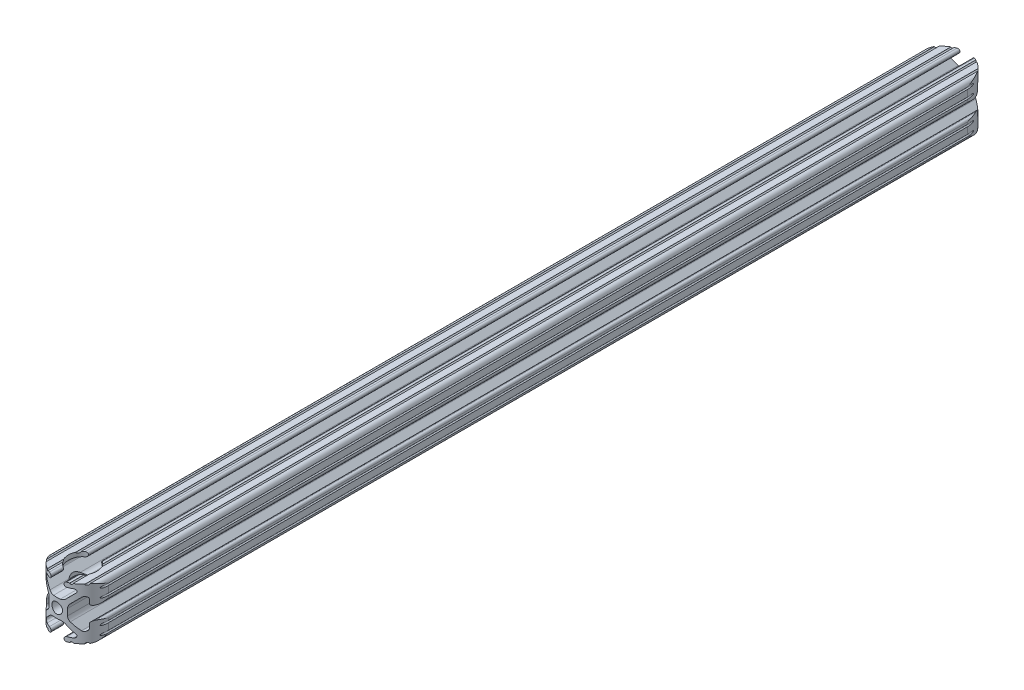
SolidWorks part; units mm, degrees
material "6063-T6"
ref_plane "Front Plane" through (0, 0, 0) normal (0, 0, 1) x (1, 0, 0)
ref_plane "Top Plane" through (0, 0, 0) normal (0, 1, 0) x (1, 0, 0)
ref_plane "Right Plane" through (0, 0, 0) normal (1, 0, 0) x (0, 0, -1)
sketch "Sketch1" plane through (0, 0, 0) normal (0, 0, 1) x (1, 0, 0)
  line L88 (-7.1797, -8.6452) -> (-3.9523, -5.4237)
  line L89 (-1.7093, -4.4958) -> (1.7093, -4.4958)
  line L90 (3.9523, -5.4237) -> (7.1797, -8.6452)
  line L91 (6.4164, -10.4902) -> (4.2875, -10.4902)
  line L92 (3.2385, -11.5392) -> (3.2385, -11.651)
  line L93 (4.2875, -12.7) -> (5.3171, -12.7)
  line L94 (6.3331, -12.7) -> (9.5504, -12.7)
  line L95 (12.7, -9.5504) -> (12.7, -6.3331)
  line L96 (12.7, -5.3171) -> (12.7, -4.2875)
  line L97 (11.651, -3.2385) -> (11.5392, -3.2385)
  line L98 (10.4902, -4.2875) -> (10.4902, -6.4021)
  line L99 (8.7371, -7.1294) -> (5.441, -3.8408)
  line L100 (4.5085, -1.5932) -> (4.5085, 1.5932)
  line L101 (5.441, 3.8408) -> (8.7371, 7.1294)
  line L102 (10.4902, 6.4021) -> (10.4902, 4.2875)
  line L103 (11.5392, 3.2385) -> (11.651, 3.2385)
  line L104 (12.7, 4.2875) -> (12.7, 5.3171)
  line L105 (12.7, 6.3331) -> (12.7, 9.5504)
  line L106 (9.5504, 12.7) -> (6.3331, 12.7)
  line L107 (5.3171, 12.7) -> (4.2875, 12.7)
  line L108 (3.2385, 11.651) -> (3.2385, 11.5392)
  line L109 (4.2875, 10.4902) -> (6.4768, 10.4902)
  line L110 (7.207, 8.7244) -> (3.8983, 5.4232)
  line L111 (1.6558, 4.4958) -> (-1.6558, 4.4958)
  line L112 (-3.8983, 5.4232) -> (-7.207, 8.7244)
  line L113 (-6.4768, 10.4902) -> (-4.2875, 10.4902)
  line L114 (-3.2385, 11.5392) -> (-3.2385, 11.651)
  line L115 (-4.2875, 12.7) -> (-5.3171, 12.7)
  line L116 (-6.3331, 12.7) -> (-9.5504, 12.7)
  line L117 (-12.7, 9.5504) -> (-12.7, 6.3331)
  line L118 (-12.7, 5.3171) -> (-12.7, 4.2875)
  line L119 (-11.651, 3.2385) -> (-11.5392, 3.2385)
  line L120 (-10.4902, 4.2875) -> (-10.4902, 6.4021)
  line L121 (-8.7371, 7.1294) -> (-5.441, 3.8408)
  line L122 (-4.5085, 1.5932) -> (-4.5085, -1.5932)
  line L123 (-5.441, -3.8408) -> (-8.7371, -7.1294)
  line L124 (-10.4902, -6.4021) -> (-10.4902, -4.2875)
  line L125 (-11.5392, -3.2385) -> (-11.651, -3.2385)
  line L126 (-12.7, -4.2875) -> (-12.7, -5.3171)
  line L127 (-12.7, -6.3331) -> (-12.7, -9.5504)
  line L128 (-9.5504, -12.7) -> (-6.3331, -12.7)
  line L129 (-5.3171, -12.7) -> (-4.2875, -12.7)
  line L130 (-3.2385, -11.651) -> (-3.2385, -11.5392)
  line L131 (-4.2875, -10.4902) -> (-6.4164, -10.4902)
  circle A1 centre (0, 0) radius 2.6035
  arc A104 (-7.1797, -8.6452) -> (-6.4164, -10.4902) centre (-6.4164, -9.4098) ccw
  arc A105 (-1.7093, -4.4958) -> (-3.9523, -5.4237) centre (-1.7093, -7.6708) ccw
  arc A106 (3.9523, -5.4237) -> (1.7093, -4.4958) centre (1.7093, -7.6708) ccw
  arc A107 (6.4164, -10.4902) -> (7.1797, -8.6452) centre (6.4164, -9.4098) ccw
  arc A108 (4.2875, -10.4902) -> (3.2385, -11.5392) centre (4.2875, -11.5392) ccw
  arc A109 (3.2385, -11.651) -> (4.2875, -12.7) centre (4.2875, -11.651) ccw
  arc A110 (6.3331, -12.7) -> (5.3171, -12.7) centre (5.8251, -12.7) ccw
  arc A111 (10.5664, -12.6998) -> (9.5504, -12.7) centre (10.0584, -12.7) ccw
  arc A112 (10.5664, -12.6998) -> (12.6998, -10.5664) centre (10.5918, -10.5918) ccw
  arc A113 (12.7, -9.5504) -> (12.6998, -10.5664) centre (12.7, -10.0584) ccw
  arc A114 (12.7, -5.3171) -> (12.7, -6.3331) centre (12.7, -5.8251) ccw
  arc A115 (12.7, -4.2875) -> (11.651, -3.2385) centre (11.651, -4.2875) ccw
  arc A116 (11.5392, -3.2385) -> (10.4902, -4.2875) centre (11.5392, -4.2875) ccw
  arc A117 (8.7371, -7.1294) -> (10.4902, -6.4021) centre (9.4628, -6.4021) ccw
  arc A118 (4.5085, -1.5932) -> (5.441, -3.8408) centre (7.6835, -1.5932) ccw
  arc A119 (5.441, 3.8408) -> (4.5085, 1.5932) centre (7.6835, 1.5932) ccw
  arc A120 (10.4902, 6.4021) -> (8.7371, 7.1294) centre (9.4628, 6.4021) ccw
  arc A121 (10.4902, 4.2875) -> (11.5392, 3.2385) centre (11.5392, 4.2875) ccw
  arc A122 (11.651, 3.2385) -> (12.7, 4.2875) centre (11.651, 4.2875) ccw
  arc A123 (12.7, 6.3331) -> (12.7, 5.3171) centre (12.7, 5.8251) ccw
  arc A124 (12.6998, 10.5664) -> (12.7, 9.5504) centre (12.7, 10.0584) ccw
  arc A125 (12.6998, 10.5664) -> (10.5664, 12.6998) centre (10.5918, 10.5918) ccw
  arc A126 (9.5504, 12.7) -> (10.5664, 12.6998) centre (10.0584, 12.7) ccw
  arc A127 (5.3171, 12.7) -> (6.3331, 12.7) centre (5.8251, 12.7) ccw
  arc A128 (4.2875, 12.7) -> (3.2385, 11.651) centre (4.2875, 11.651) ccw
  arc A129 (3.2385, 11.5392) -> (4.2875, 10.4902) centre (4.2875, 11.5392) ccw
  arc A130 (7.207, 8.7244) -> (6.4768, 10.4902) centre (6.4768, 9.4563) ccw
  arc A131 (1.6558, 4.4958) -> (3.8983, 5.4232) centre (1.6558, 7.6708) ccw
  arc A132 (-3.8983, 5.4232) -> (-1.6558, 4.4958) centre (-1.6558, 7.6708) ccw
  arc A133 (-6.4768, 10.4902) -> (-7.207, 8.7244) centre (-6.4768, 9.4563) ccw
  arc A134 (-4.2875, 10.4902) -> (-3.2385, 11.5392) centre (-4.2875, 11.5392) ccw
  arc A135 (-3.2385, 11.651) -> (-4.2875, 12.7) centre (-4.2875, 11.651) ccw
  arc A136 (-6.3331, 12.7) -> (-5.3171, 12.7) centre (-5.8251, 12.7) ccw
  arc A137 (-10.5664, 12.6998) -> (-9.5504, 12.7) centre (-10.0584, 12.7) ccw
  arc A138 (-10.5664, 12.6998) -> (-12.6998, 10.5664) centre (-10.5918, 10.5918) ccw
  arc A139 (-12.7, 9.5504) -> (-12.6998, 10.5664) centre (-12.7, 10.0584) ccw
  arc A140 (-12.7, 5.3171) -> (-12.7, 6.3331) centre (-12.7, 5.8251) ccw
  arc A141 (-12.7, 4.2875) -> (-11.651, 3.2385) centre (-11.651, 4.2875) ccw
  arc A142 (-11.5392, 3.2385) -> (-10.4902, 4.2875) centre (-11.5392, 4.2875) ccw
  arc A143 (-8.7371, 7.1294) -> (-10.4902, 6.4021) centre (-9.4628, 6.4021) ccw
  arc A144 (-4.5085, 1.5932) -> (-5.441, 3.8408) centre (-7.6835, 1.5932) ccw
  arc A145 (-5.441, -3.8408) -> (-4.5085, -1.5932) centre (-7.6835, -1.5932) ccw
  arc A146 (-10.4902, -6.4021) -> (-8.7371, -7.1294) centre (-9.4628, -6.4021) ccw
  arc A147 (-10.4902, -4.2875) -> (-11.5392, -3.2385) centre (-11.5392, -4.2875) ccw
  arc A148 (-11.651, -3.2385) -> (-12.7, -4.2875) centre (-11.651, -4.2875) ccw
  arc A149 (-12.7, -6.3331) -> (-12.7, -5.3171) centre (-12.7, -5.8251) ccw
  arc A150 (-12.6998, -10.5664) -> (-12.7, -9.5504) centre (-12.7, -10.0584) ccw
  arc A151 (-12.6998, -10.5664) -> (-10.5664, -12.6998) centre (-10.5918, -10.5918) ccw
  arc A152 (-9.5504, -12.7) -> (-10.5664, -12.6998) centre (-10.0584, -12.7) ccw
  arc A153 (-5.3171, -12.7) -> (-6.3331, -12.7) centre (-5.8251, -12.7) ccw
  arc A154 (-4.2875, -12.7) -> (-3.2385, -11.651) centre (-4.2875, -11.651) ccw
  arc A155 (-3.2385, -11.5392) -> (-4.2875, -10.4902) centre (-4.2875, -11.5392) ccw
extrude "Boss-Extrude1" add sketch "Sketch1" along normal mid plane 447.675
sketch "Sketch2" plane through (0, 12.7, 0) normal (0, 1, 0) x (1, 0, 0)
  line L0 (0, 223.8375) -> (0, -223.8375) construction
  line L1 (-12.7, 223.8375) -> (12.7, 223.8375)
  line L2 (-12.7, 223.8375) -> (-12.7, -223.8375)
  line L3 (-12.7, -223.8375) -> (12.7, -223.8375)
  line L4 (12.7, 223.8375) -> (12.7, -223.8375)
  circle A0 centre (0, 211.1375) radius 12.7
  circle A1 centre (0, -211.1375) radius 12.7
  circle A2 centre (0, -211.1375) radius 3.175
  line M5 (-6.3331, 223.8375) -> (-9.5504, 223.8375)
  line M6 (-9.5504, 223.8375) -> (-9.5504, -223.8375)
  line M7 (-9.5504, -223.8375) -> (-6.3331, -223.8375)
  line M8 (-6.3331, -223.8375) -> (-6.3331, 223.8375)
  dimension "D1" = 6.35
extrude "Cut-Extrude1" cut sketch "Sketch2" against normal through all both and the other way through all contours A2 L0 | L0 A2 | A1 L2 L3 M6 | A1 M6 M7 M8 | A1 L3 M8 | A1 L3 L4 | A0 L4 L1 | A0 M8 M5 M6 | A0 L1 M8 | A0 L1 L2 M6 region at (-4.7717, 12.7, -223.3363) region at (9.8632, 12.7, -221.0007) region at (-8.1865, 12.7, -222.3063) region at (-11.3727, 12.7, -220.0831) region at (9.8632, 12.7, 221.0007) region at (1.3475, 12.7, 211.1375) region at (-1.3475, 12.7, 211.1375) region at (-4.7717, 12.7, 223.3363) region at (-8.1865, 12.7, 222.3063) region at (-11.3727, 12.7, 220.0831)
sketch "Sketch3" plane through (0, 12.7, 0) normal (0, 1, 0) x (1, 0, 0)
  circle A0 centre (0, -211.1375) radius 6.35 construction
  circle A1 centre (0, -211.1375) radius 4.8006
  circle A2 centre (0, -211.1375) radius 6.985
  line M5 (6.3331, 222.1457) -> (6.3331, -222.1457)
  dimension "D1" = 12.7
  dimension "D2" = 9.6012
  dimension "D3" = 0.635
extrude "Cut-Extrude2" cut sketch "Sketch3" against normal up to vertex (8.2042 mm away) contours A1 | A0 A1 M5 | A2 M5 region at (0, 12.7, 211.1375) region at (6.5949, 12.7, 211.1375) region at (6.1401, 12.7, 211.1375) up to point (-7.207, 8.7244, 221.5945)
extrude "Cut-Extrude4" cut sketch "Sketch3<3>" along normal blind 3.9756 from surface contours A1 | A0 A1 M5 | A2 M5 region at (0, 12.7, 211.1375) region at (6.5949, 12.7, 211.1375) region at (6.1401, 12.7, 211.1375) starting at face at (7.9961, -12.7, 0)
sketch "Sketch3<3>" plane through (0, 12.7, 0) normal (0, 1, 0) x (1, 0, 0) same geometry as "Sketch3"
extrude "Cut-Extrude5" cut sketch "Sketch3<5>" against normal up to surface (8.2042 mm away) contours A1 region at (0, 12.7, 211.1375) up to face at (0, 4.4958, 218.9314)
sketch "Sketch3<5>" plane through (0, 12.7, 0) normal (0, 1, 0) x (1, 0, 0) same geometry as "Sketch3"
extrude "Cut-Extrude6" cut sketch "Sketch3<6>" along normal up to surface (8.2042 mm away) from surface contours A1 region at (0, 12.7, 211.1375) up to face at (0, -4.4958, 218.9213) starting at face at (7.5504, -12.7, 70.3792)
sketch "Sketch3<6>" plane through (0, 12.7, 0) normal (0, 1, 0) x (1, 0, 0) same geometry as "Sketch3"
